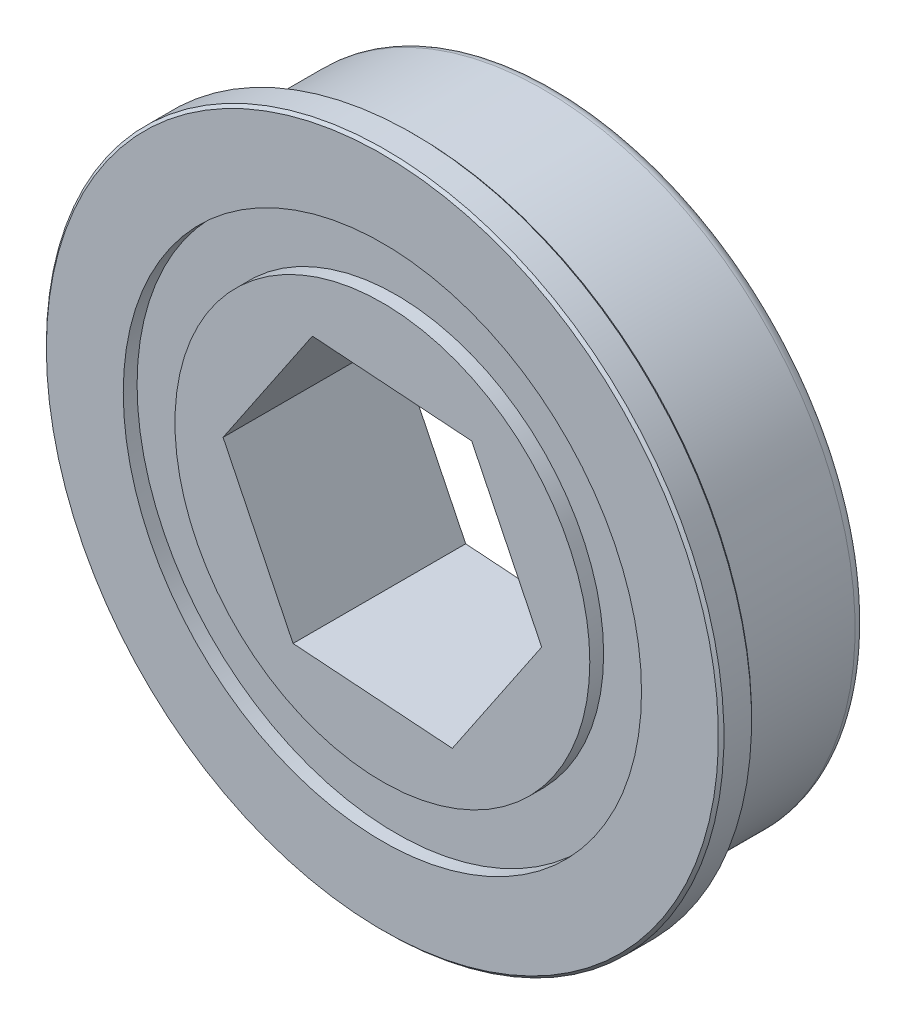
SolidWorks part; units mm, degrees
ref_plane "Front" through (0, 0, 0) normal (0, 0, 1) x (1, 0, 0)
ref_plane "Top" through (0, 0, 0) normal (0, 1, 0) x (1, 0, 0)
ref_plane "Right" through (0, 0, 0) normal (1, 0, 0) x (0, 0, -1)
ref_plane "Plane1" through (0, 0, 0) normal (0, -1, 0) x (1, 0, 0)
sketch "Sketch1" plane through (0, 0, 0) normal (0, -1, 0) x (1, 0, 0)
  line L0 (15.4305, 7.9273) -> (0, 7.9273)
  line L1 (0, 7.9273) -> (0, 0)
  line L2 (0, 0) -> (14.2875, 0)
  line L3 (14.2875, 0) -> (14.2875, 5.8953)
  line L4 (14.2875, 5.8953) -> (13.97, 5.8953)
  line L5 (13.97, 5.8953) -> (13.97, 6.4033)
  line L6 (13.97, 6.4033) -> (15.5575, 6.4033)
  line L7 (15.5575, 6.4033) -> (15.5575, 7.8003)
  line L8 (15.5575, 7.8003) -> (15.4305, 7.9273)
  line L9 (0, 7.9273) -> (0, 0) construction
revolve "Revolve1" add sketch "Sketch1" angle 360 about L9 reverse direction yes
chamfer "Chamfer1" distance 0.127 angle 45 1 edges at (-15.5575, 0, 6.4033)
fillet "Fillet2" radius 0.508 1 edges at (-14.2875, 0, 0) tangent propagation no
sketch "Sketch3" plane through (0, 0, 7.9273) normal (0, 0, 1) x (1, 0, 0)
  circle A0 centre (0, 0) radius 11.8991
extrude "Cut-Extrude2" cut sketch "Sketch3" against normal up to next
sketch "Sketch4" plane through (0, 0, 0) normal (0, 0, -1) x (-1, 0, 0)
  line L1 (-3.2123, -6.5913) -> (4.1021, -6.0775)
  line L2 (4.1021, -6.0775) -> (7.3143, 0.5137)
  line L3 (7.3143, 0.5137) -> (3.2123, 6.5913)
  line L4 (3.2123, 6.5913) -> (-4.1021, 6.0775)
  line L5 (-4.1021, 6.0775) -> (-7.3143, -0.5137)
  line L6 (-7.3143, -0.5137) -> (-3.2123, -6.5913)
  circle A0 centre (0, 0) radius 6.35 construction
  circle A1 centre (0, 0) radius 9.525
  dimension "D1" = 19.05
extrude "Boss-Extrude1" add sketch "Sketch4" against normal up to surface (7.9273 mm away) separate body up to face at (11.8991, 0, 7.9273)
ref_plane "Plane2" through (0, 0, 0.635) normal (0, 0, -1) x (-1, 0, 0)
sketch "Sketch5" plane through (0, 0, 0.635) normal (0, 0, -1) x (-1, 0, 0)
  circle A0 centre (0, 0) radius 9.525 construction
  circle A1 centre (0, 0) radius 9.525
  circle A2 centre (0, 0) radius 11.8991 construction
  circle A3 centre (0, 0) radius 11.8991
extrude "Boss-Extrude2" add sketch "Sketch5" against normal offset from surface (6.6573 mm away) 0.635 up to face at (11.8991, 0, 7.9273)
